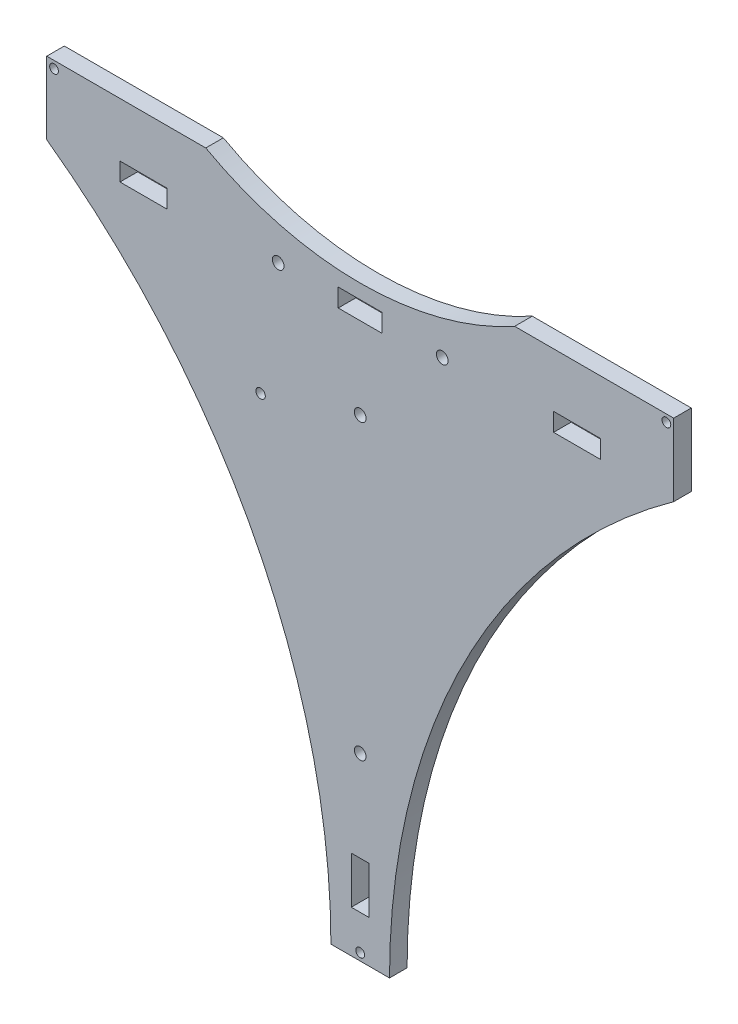
SolidWorks part; units mm, degrees
material "Oak"
ref_plane "Front Plane" through (0, 0, 0) normal (0, 0, 1) x (1, 0, 0)
ref_plane "Top Plane" through (0, 0, 0) normal (0, 1, 0) x (1, 0, 0)
ref_plane "Right Plane" through (0, 0, 0) normal (1, 0, 0) x (0, 0, -1)
sketch "Sketch1" plane through (0, 0, 0) normal (0, 0, 1) x (1, 0, 0)
  line L0 (-66, 82.3) -> (66, 82.3) construction
  line L1 (0, 82.3) -> (0, 0) construction
  line L2 (86.2011, 107) -> (107, 107)
  line L6 (0, -76.6) -> (0, -116.5) construction
  line L7 (-10, -107) -> (10, -107)
  line L8 (-107, 82.3) -> (-107, 107)
  line L9 (-107, 107) -> (-91.7989, 107)
  line L10 (107, 82.3) -> (107, 107)
  line L11 (-107, -107) -> (107, 107) construction
  line L12 (-107, 107) -> (107, -107) construction
  line L13 (-82, 88.5) -> (-66, 88.5)
  line L14 (-82, 88.5) -> (-82, 82.3)
  line L15 (-82, 82.3) -> (-66, 82.3)
  line L16 (-66, 88.5) -> (-66, 82.3)
  line L17 (82, 88.5) -> (66, 88.5)
  line L18 (82, 88.5) -> (82, 82.3)
  line L19 (82, 82.3) -> (66, 82.3)
  line L20 (66, 88.5) -> (66, 82.3)
  line L21 (-3.05, -92.6) -> (3.05, -92.6)
  line L22 (-3.05, -92.6) -> (-3.05, -76.6)
  line L23 (-3.05, -76.6) -> (3.05, -76.6)
  line L24 (3.05, -92.6) -> (3.05, -76.6)
  line L32 (52.7171, 107) -> (86.2011, 107)
  line L33 (-7.5, 82.3) -> (7.5, 82.3)
  line L34 (-7.5, 82.3) -> (-7.5, 88.5)
  line L35 (-7.5, 88.5) -> (7.5, 88.5)
  line L36 (7.5, 82.3) -> (7.5, 88.5)
  line L37 (-28, 85.4) -> (28, 85.4) construction
  line L38 (0, 82.3) -> (0, 88.5) construction
  line L40 (-91.7989, 107) -> (-52.7171, 107)
  circle A0 centre (-104.5, 104.5) radius 1.5
  circle A1 centre (104.5, 104.5) radius 1.5
  arc A2 (-52.7171, 107) -> (52.7171, 107) centre (0, 202.3724) ccw
  circle A3 centre (-28, 85.4) radius 2
  circle A4 centre (0, 104.5) radius 1.5 construction
  circle A5 centre (-34, 43.8) radius 1.6
  circle A6 centre (0, 54.4) radius 2
  circle A7 centre (0, -104.5) radius 1.5
  circle A9 centre (0, -45.6) radius 2
  circle A10 centre (28, 85.4) radius 2
  circle A11 centre (-104.5, 0) radius 1.5 [skipped]
  arc A12 (-10, -107) -> (-107, 82.3) centre (-243.2139, -107) ccw
  arc A13 (10, -107) -> (107, 82.3) centre (243.2139, -107) cw
  circle A14 centre (104.5, -104.5) radius 1.5 [skipped]
  circle A15 centre (-104.5, -104.5) radius 1.5 [skipped]
  circle A16 centre (104.5, 0) radius 1.5 [skipped]
  point P36 (0, 93.4)
  point P69 (0, 85.4)
  dimension "D4" = 3
  dimension "D16" = 13.6
  dimension "D23" = 28
  dimension "D10" = 4
  dimension "D11" = 100
  dimension "D19" = 3.2
  dimension "D3" = 214
  dimension "D5" = 209
  dimension "D6" = 6.2
  dimension "D7" = 16
  dimension "D8" = 18.5
  dimension "D9" = 181.1
  dimension "D12" = 20
  dimension "D13" = 4
  dimension "D14" = 31
  dimension "D15" = 214
  dimension "D17" = 82
  dimension "D21" = 15
  dimension "D22" = 6.1
  dimension "D24" = 38.5
  dimension "D25" = 34
extrude "Boss-Extrude1" add sketch "Sketch1" along normal blind 6
equation "\"bed-plate-thickness\"=6"
equation "\"D1@Boss-Extrude1\"=\"bed-plate-thickness\""
equation "\"D22@Sketch1\"=\"y-cross-rib-thickness\"+0.1"
equation "\"D6@Sketch1\"=\"y-rib-thickness\"+0.2"
equation "\"y-cross-rib-thickness\"=6"
equation "\"y-rib-thickness\"=6"
equation "\"x-plate-thickness\"=5"
equation "\"rod-diameter\"=12"
equation "\"t-nut-hole-diameter\"=3"
equation "\"D14@Sketch1\"=28+(\"y-rib-thickness\"/2)"
